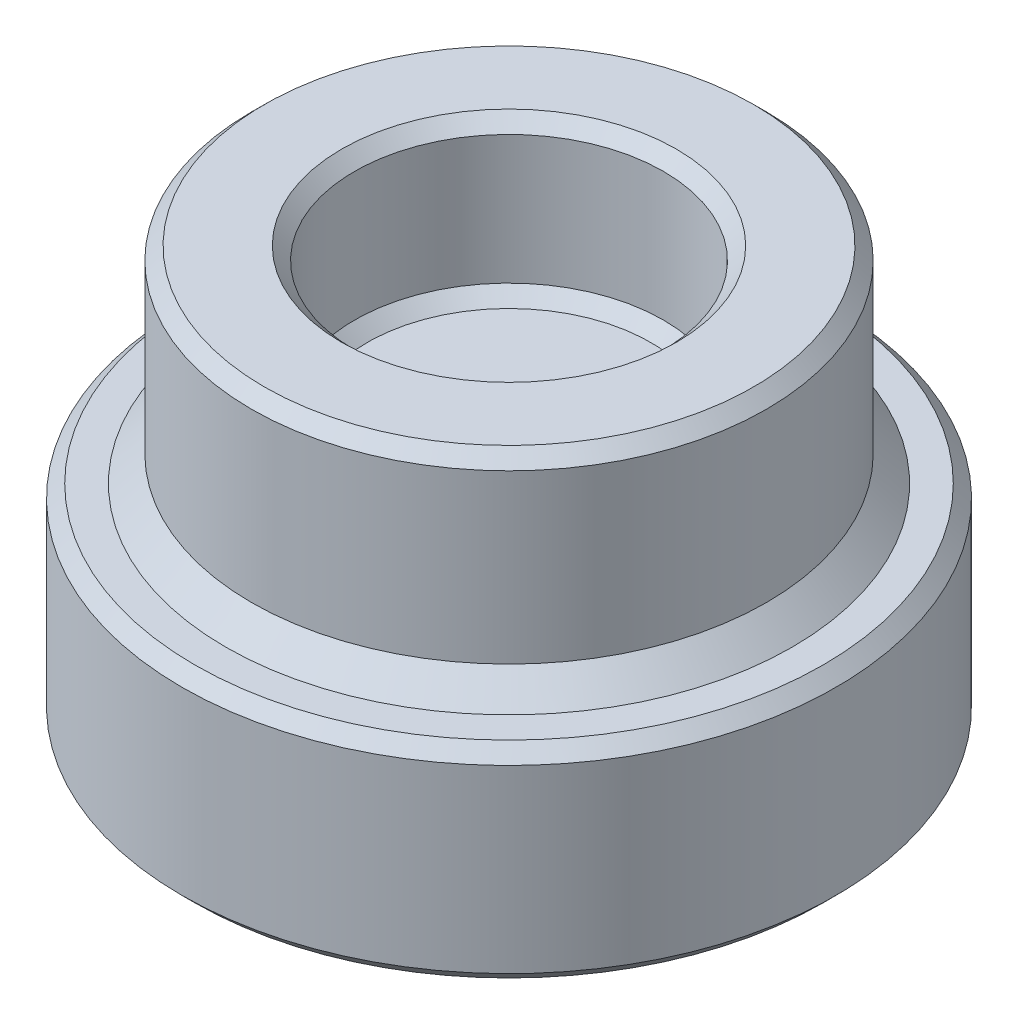
SolidWorks part; units mm, degrees
note: '?' marks a value the reader was unsure of. The reader was unsure of these and kept them because the rebuilt part matched: shared geometry of "Sketch1<3>".
material "ABS"
ref_plane "Front Plane" through (0, 0, 0) normal (0, 0, 1) x (1, 0, 0)
ref_plane "Top Plane" through (0, 0, 0) normal (0, 1, 0) x (1, 0, 0)
ref_plane "Right Plane" through (0, 0, 0) normal (1, 0, 0) x (0, 0, -1)
ref_axis "X Axis" through (88.99, 0, 0) along (-1, 0, 0)?
ref_axis "Y Axis" through (0, 55, 0) along (0, -1, 0)?
ref_axis "Z Axis" through (0, 0, -88.99) along (0, 0, 1)?
sketch "Sketch1" plane through (0, 0, 0) normal (0, 1, 0) x (1, 0, 0)
  circle A0 centre (0, 0) radius 5
  circle A1 centre (0, 0) radius 3
  dimension "D1" = 6
  dimension "D2" = 10
extrude "Boss-Extrude1" add sketch "Sketch1" along normal blind 1 contours A1 | A0 A1
extrude "Boss-Extrude2" add sketch "Sketch1<3>" along normal blind 4
sketch "Sketch1<3>" plane through (0, 0, 0) normal (0, 1, 0) x (1, 0, 0) same geometry as "Sketch1"
chamfer "Chamfer1" distance 0.25 angle 45 3 edges at (0, 4, 3) (0, 4, 5) (0, 1, 3)
sketch "Sketch5" plane through (0, 0, 0) normal (0, 1, 0) x (1, 0, 0)
  circle A0 centre (0, 0) radius 6.35
  dimension "D1" = 12.7
extrude "Boss-Extrude4" add sketch "Sketch5" against normal blind 4
sketch "Sketch4" plane through (0, -4, 0) normal (0, -1, 0) x (-1, 0, 0)
  point P0 (0, 0)
hole_wizard "Ø8.0mm Dowel Hole1" [suppressed] positions "Sketch4" profile "Sketch3" hole size "Ø8.0" standard "ANSI Metric"
sketch "Sketch3" plane through (0, -12.5, 0) normal (1, 0, 0) x (0, 0, -1)
  line L0 (0, 0) -> (0, 12.5)
  line L1 (0, 12.5) -> (4, 12.15)
  line L2 (4, 12.15) -> (4, 0.5)
  line L3 (4, 0.5) -> (4.5, 0)
  line L5 (4.5, 0) -> (0, 0)
  line L6 (-4, 0.5) -> (-4.5, 0) construction
  line L10 (0, 12.5) -> (-4, 12.15) construction
  line L11 (0, -6.35) -> (0, 107.95) construction
  dimension "Hole Dia." = 8
  dimension "Hole Depth" = 12.5
  dimension "Near C'Sink Dia." = 9
  dimension "Near C'Sink Angle" = 90
  dimension "Drill Angle" = 170
sketch "Sketch8" plane through (0, -4, 0) normal (0, -1, 0) x (-1, 0, 0)
  point P0 (0, 0)
hole_wizard "Ø3.5 (3.5) Diameter Hole1" [suppressed] positions "Sketch8" profile "Sketch7" hole size "Ø3.5" standard "ANSI Metric"
sketch "Sketch7" plane through (0, -4.7625, 0) normal (1, 0, 0) x (0, 0, -1)
  line L0 (0, 0) -> (0, 4.76)
  line L1 (0, 4.76) -> (1.75, 4.4514)
  line L2 (1.75, 4.4514) -> (1.75, 0.25)
  line L3 (1.75, 0.25) -> (2, 0)
  line L5 (2, 0) -> (0, 0)
  line L6 (-1.75, 0.25) -> (-2, 0) construction
  line L10 (0, 4.76) -> (-1.75, 4.4514) construction
  line L11 (0, -6.35) -> (0, 107.95) construction
  dimension "Hole Dia." = 3.5
  dimension "Hole Depth" = 4.76
  dimension "Near C'Sink Dia." = 4
  dimension "Near C'Sink Angle" = 90
  dimension "Drill Angle" = 160
sketch "Sketch11" plane through (0, -4, 0) normal (0, -1, 0) x (-1, 0, 0)
  point P0 (0, 0)
hole_wizard "Ø6.0mm Dowel Hole1" positions "Sketch11" profile "Sketch10" hole size "Ø6.0" standard "ANSI Metric"
sketch "Sketch10" plane through (0, -4, 0) normal (1, 0, 0) x (0, 0, -1)
  line L0 (0, 0) -> (0, 4)
  line L1 (0, 4) -> (3, 3.7375)
  line L2 (3, 3.7375) -> (3, 0.125)
  line L3 (3, 0.125) -> (3.125, 0)
  line L5 (3.125, 0) -> (0, 0)
  line L6 (-3, 0.125) -> (-3.125, 0) construction
  line L10 (0, 4) -> (-3, 3.7375) construction
  line L11 (0, -6.35) -> (0, 107.95) construction
  dimension "Hole Dia." = 6
  dimension "Hole Depth" = 4
  dimension "Near C'Sink Dia." = 6.25
  dimension "Near C'Sink Angle" = 90
  dimension "Drill Angle" = 170
chamfer "Chamfer2" distance 0.25 angle 45 2 edges at (0, -4, 6.35) (0, 0, 6.35)
chamfer "Chamfer3" distance 0.5 angle 45 1 edges at (0, 0, 5)
